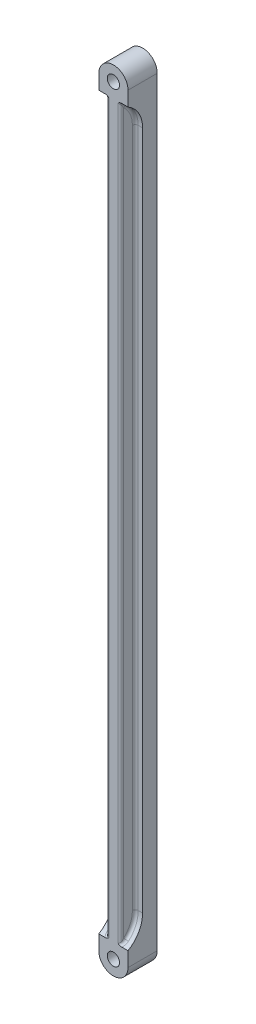
SolidWorks part; units mm, degrees
ref_plane "前视基准面" through (0, 0, 0) normal (0, 0, 1) x (1, 0, 0)
ref_plane "上视基准面" through (0, 0, 0) normal (0, 1, 0) x (1, 0, 0)
ref_plane "右视基准面" through (0, 0, 0) normal (1, 0, 0) x (0, 0, -1)
other "Configuration Table"
sketch "草图1" plane through (0, 0, 0) normal (0, 0, 1) x (1, 0, 0)
  line L1 (0, 0) -> (10, 0)
  line L2 (0, 0) -> (0, 10)
  line L3 (0, 10) -> (10, 10)
  line L4 (10, 0) -> (10, 10)
  dimension "D1" = 10
  dimension "D2" = 10
extrude "凸台-拉伸1" add sketch "草图1" along normal blind 10
fillet "圆角1" 2 edges at (0, 0, 5) (10, 0, 5) type full round first side face at (0, 5, 5) second side face at (10, 5, 5) middle face at (5, 0, 5)
sketch "草图2" plane through (0, 0, 10) normal (0, 0, 1) x (1, 0, 0)
  circle A0 centre (5, 5) radius 2.1
  dimension "D1" = 4.2
extrude "切除-拉伸1" cut sketch "草图2" against normal through all
sketch "草图3" plane through (0, 10, 0) normal (0, 1, 0) x (1, 0, 0)
  line L0 (10, -10) -> (10, 0) construction
  line L1 (0, 0) -> (10, 0)
  line L2 (0, 0) -> (0, -5)
  line L3 (0, -5) -> (10, -5)
  line L4 (10, 0) -> (10, -5)
  dimension "D1" = 5
extrude "凸台-拉伸2" add sketch "草图3" along normal blind 250
sketch "草图4" plane through (0, 260, 0) normal (0, 1, 0) x (1, 0, 0)
  line L1 (0, 0) -> (10, 0)
  line L2 (0, 0) -> (0, -10)
  line L3 (0, -10) -> (10, -10)
  line L4 (10, 0) -> (10, -10)
extrude "凸台-拉伸3" add sketch "草图4" along normal blind 10
fillet "圆角2" 2 edges at (10, 270, 5) (0, 270, 5) type full round first side face at (10, 136.25, 6.25) second side face at (0, 136.25, 6.25) middle face at (5, 270, 5)
sketch "草图5" plane through (0, 0, 10) normal (0, 0, 1) x (1, 0, 0)
  circle A0 centre (5, 265) radius 2.1
  dimension "D1" = 4.2
extrude "切除-拉伸2" cut sketch "草图5" against normal blind 10
fillet "圆角3" radius 10 2 edges at (5, 260, 5) (5, 10, 5)
sketch "草图6" plane through (0, 0, 5) normal (0, 0, 1) x (1, 0, 0)
  line L0 (0, 260) -> (10, 260) construction
  line L1 (2.5, 260) -> (7.5, 260)
  line L2 (2.5, 260) -> (2.5, 10)
  line L3 (2.5, 10) -> (7.5, 10)
  line L4 (7.5, 260) -> (7.5, 10)
  line L5 (10, 10) -> (0, 10) construction
  line L6 (10, 251.3397) -> (10, 18.6603) construction
  dimension "D1" = 5
  dimension "D2" = 2.5
extrude "凸台-拉伸4" add sketch "草图6" along normal blind 5
fillet "圆角4" radius 1 2 edges at (2.5, 135, 10) (7.5, 135, 10)
fillet "圆角5" radius 1 10 edges at (2.7269, 10.2217, 9.6343) (2.5, 14.1881, 6.0557) (2.5, 135, 5) (2.5, 255.8119, 6.0557) (7.2213, 10.1849, 9.6926) (7.5, 14.1881, 6.0557) (7.5, 135, 5) (7.2731, 259.7783, 9.6343) (2.7787, 259.8151, 9.6926) (7.5, 255.8119, 6.0557)
